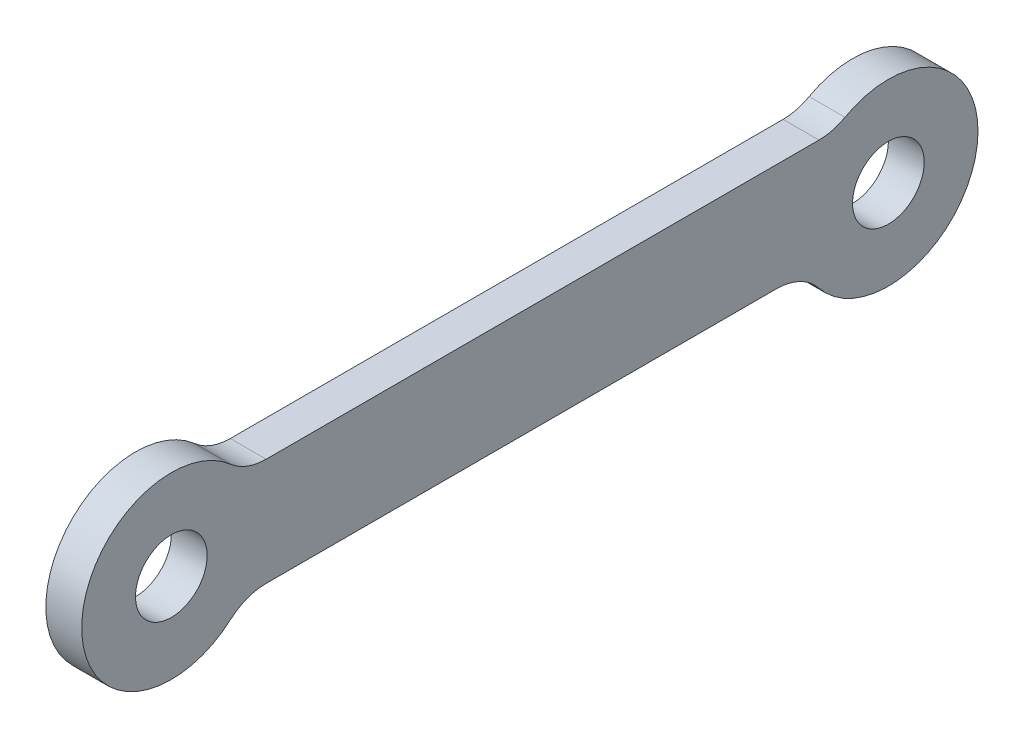
SolidWorks part; units mm, degrees
ref_plane "前视基准面" through (0, 0, 0) normal (0, 0, 1) x (1, 0, 0)
ref_plane "上视基准面" through (0, 0, 0) normal (0, 1, 0) x (1, 0, 0)
ref_plane "右视基准面" through (0, 0, 0) normal (1, 0, 0) x (0, 0, -1)
other "Configuration Table"
sketch "草图1" plane through (0, 0, 0) normal (1, 0, 0) x (0, 0, -1)
  line L1 (0, -3) -> (40, -3)
  line L2 (0, -3) -> (0, 3)
  line L3 (0, 3) -> (40, 3)
  line L4 (40, -3) -> (40, 3)
  circle A0 centre (0, 0) radius 5
  circle A1 centre (40, -1) radius 5
  circle A2 centre (0, 0) radius 2
  circle A3 centre (40, -1) radius 2
  dimension "D1" = 4
  dimension "D4" = 10
  dimension "D5" = 10
  dimension "D2" = 6
  dimension "D3" = 2
  dimension "D6" = 40
extrude "凸台-拉伸1" add sketch "草图1" along normal blind 2 contours A0 | L3 L4 L1 L2 | A1
extrude "切除-拉伸2" cut sketch "草图1<3>" against normal through all and the other way through all contours A2 | A3
sketch "草图1<3>" plane through (0, 0, 0) normal (1, 0, 0) x (0, 0, -1) same geometry as "草图1"
fillet "圆角1" radius 3 4 edges at (1, -3, -4) (1, -3, -35.4174) (1, 3, -37) (1, 3, -4)
